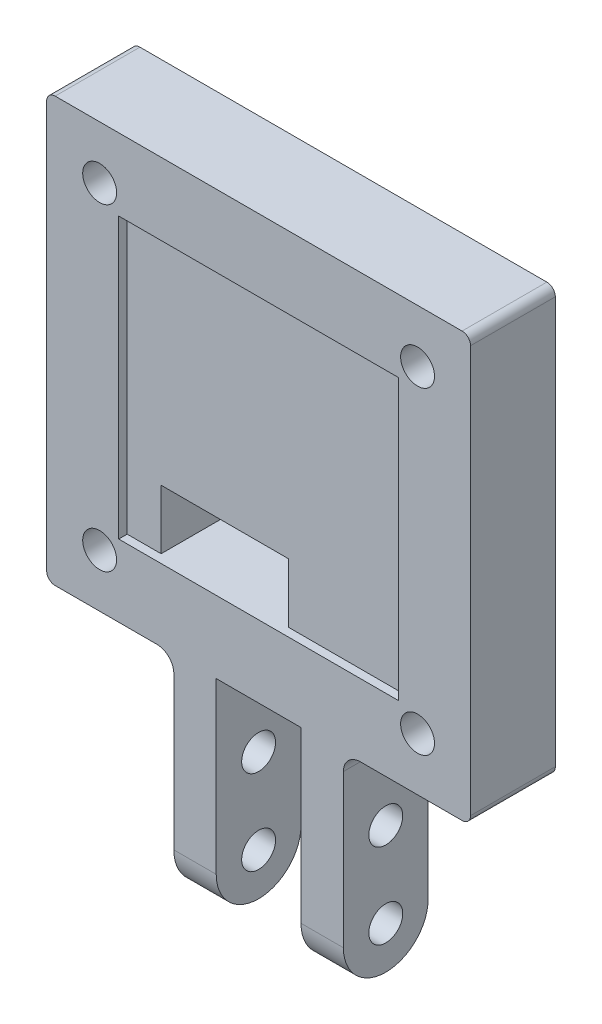
SolidWorks part; units mm, degrees
ref_plane "Front Plane" through (0, 0, 0) normal (0, 0, 1) x (1, 0, 0)
ref_plane "Top Plane" through (0, 0, 0) normal (0, 1, 0) x (1, 0, 0)
ref_plane "Right Plane" through (0, 0, 0) normal (1, 0, 0) x (0, 0, -1)
sketch "Sketch1" plane through (0, 0, 0) normal (0, 0, 1) x (1, 0, 0)
  line L0 (0, 0) -> (50, 0)
  line L1 (50, 0) -> (50, 50)
  line L2 (50, 50) -> (0, 50)
  line L3 (0, 50) -> (0, 0)
  dimension "D1" = 50
  dimension "D2" = 50
extrude "Boss-Extrude1" add sketch "Sketch1" along normal blind 10
sketch "Sketch2" plane through (0, 0, 0) normal (0, -1, 0) x (1, 0, 0)
  line L0 (15, 10) -> (15, 0)
  line L1 (0, 10) -> (50, 10) construction
  line L2 (0, 0) -> (50, 0) construction
  line L3 (0, 10) -> (0, 0) construction
  line L4 (15, 0) -> (20, 0)
  line L5 (20, 0) -> (20, 10)
  line L6 (20, 10) -> (15, 10)
  line L7 (30, 10) -> (30, 0)
  line L8 (30, 10) -> (35, 10)
  line L9 (35, 10) -> (35, 0)
  line L10 (35, 0) -> (30, 0)
  dimension "D1" = 15
  dimension "D2" = 5
  dimension "D3" = 10
  dimension "D4" = 5
extrude "Boss-Extrude2" add sketch "Sketch2" along normal blind 25
sketch "Sketch3" plane through (0, 0, 10) normal (0, 0, 1) x (1, 0, 0)
  line L0 (6.25, 43.75) -> (6.25, 6.25) construction
  line L1 (6.25, 6.25) -> (43.75, 6.25) construction
  line L2 (43.75, 6.25) -> (43.75, 43.75) construction
  line L3 (43.75, 43.75) -> (6.25, 43.75) construction
  line L5 (50, 50) -> (0, 50) construction
  line L6 (0, 50) -> (0, 0) construction
  circle A0 centre (43.75, 43.75) radius 2
  circle A1 centre (6.25, 43.75) radius 2
  circle A2 centre (6.25, 6.25) radius 2
  circle A3 centre (43.75, 6.25) radius 2
  dimension "D1" = 4
  dimension "D2" = 4
  dimension "D3" = 4
  dimension "D4" = 4
  dimension "D5" = 37.5
  dimension "D6" = 37.5
  dimension "D7" = 37.5
  dimension "D8" = 6.25
  dimension "D9" = 6.25
extrude "Cut-Extrude1" cut sketch "Sketch3" against normal blind 25
sketch "Sketch4" plane through (35, 0, 0) normal (1, 0, 0) x (0, 0, -1)
  line L0 (-10, -25) -> (-10, 0) construction
  line L1 (-10, 0) -> (0, 0) construction
  circle A0 centre (-5, -10) radius 2
  circle A1 centre (-5, -20) radius 2
  dimension "D1" = 4
  dimension "D2" = 4
  dimension "D3" = 5
  dimension "D4" = 5
  dimension "D5" = 10
  dimension "D6" = 10
extrude "Cut-Extrude2" cut sketch "Sketch4" against normal blind 25
fillet "Fillet2" radius 5 1 edges at (32.5, -25, 10)
fillet "Fillet3" radius 5 3 edges at (17.5, -25, 10) (17.5, -25, 0) (32.5, -25, 0)
fillet "Fillet4" radius 1 4 edges at (50, 0, 5) (0, 0, 5) (0, 50, 5) (50, 50, 5)
fillet "Fillet5" radius 2 1 edges at (15, 0, 5)
fillet "Fillet6" radius 2 1 edges at (35, 0, 5)
sketch "Sketch5" plane through (0, 0, 10) normal (0, 0, 1) x (1, 0, 0)
  line L0 (50, 1) -> (50, 49) construction
  line L1 (8.5, 8.5) -> (41.5, 8.5)
  line L2 (8.5, 8.5) -> (8.5, 41.5)
  line L3 (8.5, 41.5) -> (41.5, 41.5)
  line L4 (41.5, 8.5) -> (41.5, 41.5)
  line L5 (8.5, 8.5) -> (41.5, 41.5) construction
  line L6 (8.5, 41.5) -> (41.5, 8.5) construction
  line L7 (49, 50) -> (1, 50) construction
  point P0 (25, 25)
  dimension "D1" = 33
  dimension "D2" = 33
  dimension "D3" = 8.5
  dimension "D4" = 8.5
extrude "Cut-Extrude3" cut sketch "Sketch5" against normal blind 1
sketch "Sketch6" plane through (0, 0, 9) normal (0, 0, 1) x (1, 0, 0)
  line L0 (8.5, 8.5) -> (41.5, 8.5) construction
  line L1 (12.5, 8.5) -> (27.5, 8.5)
  line L2 (12.5, 8.5) -> (12.5, 15.5)
  line L3 (12.5, 15.5) -> (27.5, 15.5)
  line L4 (27.5, 8.5) -> (27.5, 15.5)
  line L5 (8.5, 41.5) -> (8.5, 8.5) construction
  dimension "D1" = 15
  dimension "D2" = 7
  dimension "D3" = 4
extrude "Cut-Extrude4" cut sketch "Sketch6" against normal blind 16
